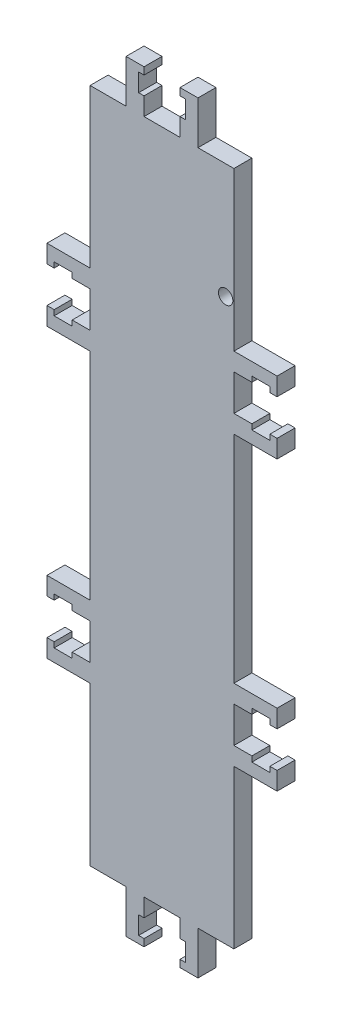
SolidWorks part; units mm, degrees
ref_plane "Plan de face" through (0, 0, 0) normal (0, 0, 1) x (1, 0, 0)
ref_plane "Plan de dessus" through (0, 0, 0) normal (0, 1, 0) x (1, 0, 0)
ref_plane "Plan de droite" through (0, 0, 0) normal (1, 0, 0) x (0, 0, -1)
sketch "Esquisse1" plane through (0, 0, 0) normal (0, 0, 1) x (1, 0, 0)
  line L0 (0, 0) -> (0, 94) construction
  line L1 (-22.1872, 94) -> (27.2472, 94) construction
  line L2 (-10, 188) -> (-20, 188)
  line L3 (-20, 188) -> (-20, 0) construction
  line L4 (-20, 0) -> (-10, 0)
  line L5 (10, 0) -> (20, 0)
  line L6 (-20, 0) -> (-20, 44)
  line L7 (20, 0) -> (20, 188) construction
  line L8 (-20, 64) -> (-20, 124)
  line L9 (20, 188) -> (10, 188)
  line L10 (20, 0) -> (20, 44)
  line L11 (-20, 144) -> (-20, 188)
  line L12 (20, 64) -> (20, 124)
  line L13 (20, 144) -> (20, 188)
  circle A0 centre (17.7, 156) radius 2
  point P18 (-20, 154)
  line B0 (0, 188) -> (0, 176.135) construction
  line B1 (0, 188) -> (-5, 188)
  line B2 (-5, 193) -> (-10, 193) construction
  line B3 (-10, 193) -> (-10, 188)
  line B4 (-5, 193) -> (-5, 188)
  line B5 (0, 188) -> (5, 188)
  line B6 (5, 188) -> (5, 193)
  line B7 (5, 193) -> (10, 193) construction
  line B8 (10, 193) -> (10, 188)
  line B9 (-10, 193) -> (-10, 200)
  line B10 (-10, 200) -> (-5, 200)
  line B11 (-5, 200) -> (-5, 198)
  line B12 (-5, 198) -> (-6.5, 198)
  line B13 (-6.5, 198) -> (-6.5, 193)
  line B14 (-6.5, 193) -> (-5, 193)
  line B15 (5, 198) -> (6.5, 198)
  line B16 (10, 200) -> (5, 200)
  line B17 (5, 200) -> (5, 198)
  line B18 (6.5, 198) -> (6.5, 193)
  line B19 (10, 193) -> (10, 200)
  line B20 (10, 193) -> (10, 188)
  line B21 (5, 193) -> (6.5, 193)
  line B22 (0, 0) -> (0, 11.865) construction
  line B23 (0, 0) -> (-5, 0)
  line B24 (-5, -5) -> (-10, -5) construction
  line B25 (-10, -5) -> (-10, 0)
  line B26 (-5, -5) -> (-5, 0)
  line B27 (0, 0) -> (5, 0)
  line B28 (5, 0) -> (5, -5)
  line B29 (5, -5) -> (10, -5) construction
  line B30 (10, -5) -> (10, 0)
  line B31 (-10, -5) -> (-10, -12)
  line B32 (-10, -12) -> (-5, -12)
  line B33 (-5, -12) -> (-5, -10)
  line B34 (-5, -10) -> (-6.5, -10)
  line B35 (-6.5, -10) -> (-6.5, -5)
  line B36 (-6.5, -5) -> (-5, -5)
  line B37 (5, -10) -> (6.5, -10)
  line B38 (10, -12) -> (5, -12)
  line B39 (5, -12) -> (5, -10)
  line B40 (6.5, -10) -> (6.5, -5)
  line B41 (10, -5) -> (10, -12)
  line B42 (10, -5) -> (10, 0)
  line B43 (5, -5) -> (6.5, -5)
  line B44 (-20, 134) -> (-8.135, 134) construction
  line B45 (-20, 134) -> (-20, 129)
  line B46 (-25, 129) -> (-25, 124) construction
  line B47 (-25, 124) -> (-20, 124)
  line B48 (-25, 129) -> (-20, 129)
  line B49 (-20, 134) -> (-20, 139)
  line B50 (-20, 139) -> (-25, 139)
  line B51 (-25, 139) -> (-25, 144) construction
  line B52 (-25, 144) -> (-20, 144)
  line B53 (-25, 124) -> (-32, 124)
  line B54 (-32, 124) -> (-32, 129)
  line B55 (-32, 129) -> (-30, 129)
  line B56 (-30, 129) -> (-30, 127.5)
  line B57 (-30, 127.5) -> (-25, 127.5)
  line B58 (-25, 127.5) -> (-25, 129)
  line B59 (-30, 139) -> (-30, 140.5)
  line B60 (-32, 144) -> (-32, 139)
  line B61 (-32, 139) -> (-30, 139)
  line B62 (-30, 140.5) -> (-25, 140.5)
  line B63 (-25, 144) -> (-32, 144)
  line B64 (-25, 144) -> (-20, 144)
  line B65 (-25, 139) -> (-25, 140.5)
  line B66 (-20, 54) -> (-8.135, 54) construction
  line B67 (-20, 54) -> (-20, 59)
  line B68 (-25, 59) -> (-25, 64) construction
  line B69 (-25, 64) -> (-20, 64)
  line B70 (-25, 59) -> (-20, 59)
  line B71 (-20, 54) -> (-20, 49)
  line B72 (-20, 49) -> (-25, 49)
  line B73 (-25, 49) -> (-25, 44) construction
  line B74 (-25, 44) -> (-20, 44)
  line B75 (-25, 64) -> (-32, 64)
  line B76 (-32, 64) -> (-32, 59)
  line B77 (-32, 59) -> (-30, 59)
  line B78 (-30, 59) -> (-30, 60.5)
  line B79 (-30, 60.5) -> (-25, 60.5)
  line B80 (-25, 60.5) -> (-25, 59)
  line B81 (-30, 49) -> (-30, 47.5)
  line B82 (-32, 44) -> (-32, 49)
  line B83 (-32, 49) -> (-30, 49)
  line B84 (-30, 47.5) -> (-25, 47.5)
  line B85 (-25, 44) -> (-32, 44)
  line B86 (-25, 44) -> (-20, 44)
  line B87 (-25, 49) -> (-25, 47.5)
  line B88 (20, 54) -> (8.135, 54) construction
  line B89 (20, 54) -> (20, 59)
  line B90 (25, 59) -> (25, 64) construction
  line B91 (25, 64) -> (20, 64)
  line B92 (25, 59) -> (20, 59)
  line B93 (20, 54) -> (20, 49)
  line B94 (20, 49) -> (25, 49)
  line B95 (25, 49) -> (25, 44) construction
  line B96 (25, 44) -> (20, 44)
  line B97 (25, 64) -> (32, 64)
  line B98 (32, 64) -> (32, 59)
  line B99 (32, 59) -> (30, 59)
  line B100 (30, 59) -> (30, 60.5)
  line B101 (30, 60.5) -> (25, 60.5)
  line B102 (25, 60.5) -> (25, 59)
  line B103 (30, 49) -> (30, 47.5)
  line B104 (32, 44) -> (32, 49)
  line B105 (32, 49) -> (30, 49)
  line B106 (30, 47.5) -> (25, 47.5)
  line B107 (25, 44) -> (32, 44)
  line B108 (25, 44) -> (20, 44)
  line B109 (25, 49) -> (25, 47.5)
  line B110 (20, 134) -> (8.135, 134) construction
  line B111 (20, 134) -> (20, 129)
  line B112 (25, 129) -> (25, 124) construction
  line B113 (25, 124) -> (20, 124)
  line B114 (25, 129) -> (20, 129)
  line B115 (20, 134) -> (20, 139)
  line B116 (20, 139) -> (25, 139)
  line B117 (25, 139) -> (25, 144) construction
  line B118 (25, 144) -> (20, 144)
  line B119 (25, 124) -> (32, 124)
  line B120 (32, 124) -> (32, 129)
  line B121 (32, 129) -> (30, 129)
  line B122 (30, 129) -> (30, 127.5)
  line B123 (30, 127.5) -> (25, 127.5)
  line B124 (25, 127.5) -> (25, 129)
  line B125 (30, 139) -> (30, 140.5)
  line B126 (32, 144) -> (32, 139)
  line B127 (32, 139) -> (30, 139)
  line B128 (30, 140.5) -> (25, 140.5)
  line B129 (25, 144) -> (32, 144)
  line B130 (25, 144) -> (20, 144)
  line B131 (25, 139) -> (25, 140.5)
  dimension "D3" = 4
  dimension "D4" = 188
  dimension "D1" = 20
  dimension "D5" = 2.3
  dimension "D6" = 32
  dimension "D7" = 40
sketch_block_instance "Insert plots ep 5mm avec ergots-8"
sketch_block "Insert plots ep 5mm avec ergots" parameters "D1"=10, "D2"=5, "D3"=5, "D4"=5, "D5"=2, "D6"=1.5, "D7"=2, "D8"=2, "D9"=2.0716, "D10"=2
sketch_block_instance "Insert plots ep 5mm avec ergots-9"
sketch_block_instance "Insert plots ep 5mm avec ergots-11"
sketch_block_instance "Insert plots ep 5mm avec ergots-12"
sketch_block_instance "Insert plots ep 5mm avec ergots-15"
sketch_block_instance "Insert plots ep 5mm avec ergots-16" parameters "D3"=1.9805, "D1"=0, "D2"=11.4238, "D4"=90.4393, "D5"=2.2878, "D6"=32.338, "D7"=10.0584, "D8"=60
extrude "Boss.-Extru.1" add sketch "Esquisse1" along normal blind 5 contours L2 L3 L4 L5 L7 L9 region at (-0.0273, 93.9043, 0)
